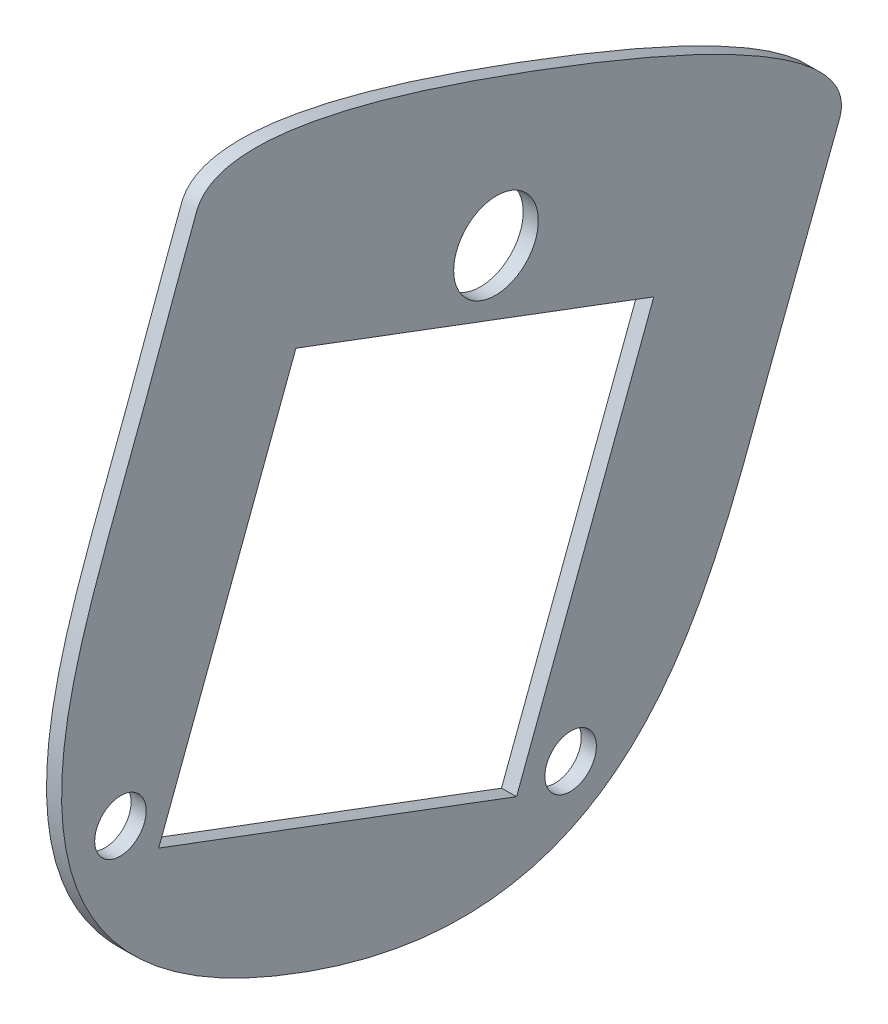
SolidWorks part; units mm, degrees
ref_plane "Front Plane" through (0, 0, 0) normal (0, 0, 1) x (1, 0, 0)
ref_plane "Top Plane" through (0, 0, 0) normal (0, 1, 0) x (1, 0, 0)
ref_plane "Right Plane" through (0, 0, 0) normal (1, 0, 0) x (0, 0, -1)
sketch "Sketch2" plane through (-865.3739, -0.0001, 10.9842) normal (-0.9999, 0, 0.0127) x (0.0127, 0, 0.9999)
  circle A0 centre (-17.1866, -9.2159) radius 6 construction
  circle A1 centre (105.1276, 37.6907) radius 6 construction
  circle A2 centre (-17.1866, -9.2159) radius 6
  circle A3 centre (105.1276, 37.6907) radius 6
  circle A4 centre (2.5155, 122.3361) radius 11.5 construction
  circle A5 centre (2.5155, 122.3361) radius 11.5
  point P0 (86.5551, 152.6282)
  point P1 (81.9504, 150.6796)
  dimension "D4" = 23
  dimension "D1" = 5
ref_plane "Plane1" through (-1179.5486, -0.0001, 14.972) normal (-0.9999, 0, 0.0127) x (0.0127, 0, 0.9999)
sketch "Sketch3" plane through (-1179.5486, -0.0001, 14.972) normal (-0.9999, 0, 0.0127) x (0.0127, 0, 0.9999)
  line L2 (-2.4987, -10.0092) -> (94.7364, 27.2797)
  line L6 (94.7364, 27.2797) -> (57.4475, 124.5149)
  line L7 (57.4475, 124.5149) -> (-39.7876, 87.2259)
  line L8 (-39.7876, 87.2259) -> (-2.4987, -10.0092)
  circle A3 centre (105.1276, 37.6907) radius 7
  circle A8 centre (3.0884, 120.8422) radius 11.5
  circle A9 centre (-17.1866, -9.2159) radius 7
  spline S0 degree 3 poles (84.5877, 169.5548) (84.1591, 170.6141) (83.6114, 171.6458) (82.4825, 172.9682) (81.1275, 174.0328) (79.6255, 174.8519) (78.0481, 175.4677) (75.8837, 176.0674) (73.1375, 176.4938) (69.8483, 176.6685) (66.5932, 176.6095) (63.379, 176.3823) (60.2073, 176.0282) (57.0754, 175.5759) (53.9806, 175.0444) (50.9193, 174.4483) (47.8886, 173.7975) (44.8855, 173.1008) (40.9147, 172.1178) (36.0066, 170.8019) (30.1862, 169.1128) (24.4167, 167.3312) (18.6809, 165.471) (12.9629, 163.5374) (7.2468, 161.5366) (-0.3928, 158.7797) (-6.166, 156.6131) (-13.9483, 153.6286) (-19.6897, 151.3795) (-27.2134, 148.3214) (-32.8014, 145.9872) (-38.3459, 143.6017) (-43.8547, 141.1498) (-49.3359, 138.6168) (-54.7932, 135.9811) (-59.3225, 133.6777) (-62.9324, 131.7536) (-65.6313, 130.2638) (-68.3201, 128.7213) (-70.995, 127.1176) (-73.6517, 125.4434) (-76.283, 123.6856) (-78.8782, 121.8282) (-81.4203, 119.8479) (-83.8804, 117.7153) (-86.2094, 115.386) (-87.9665, 113.2326) (-89.1751, 111.3395) (-89.9363, 109.8267) (-90.5056, 108.2133) (-90.8014, 106.5155) (-90.7567, 104.7772) (-90.474, 103.6437) (-90.0844, 102.5695) (-89.841, 101.912) (-89.5415, 101.1241) (-89.3902, 100.7305) (-89.238, 100.337) (-89.086, 99.9434) (-88.9335, 99.5497) (-88.7301, 99.0246) (-88.3735, 98.1053) (-87.8622, 96.7909) (-87.2459, 95.2119) (-86.6271, 93.6311) (-86.006, 92.0484) (-85.3828, 90.4637) (-84.7576, 88.8772) (-84.1306, 87.2885) (-83.5021, 85.6979) (-82.662, 83.5742) (-81.6087, 80.9142) (-80.341, 77.7134) (-79.0707, 74.5033) (-77.7994, 71.2836) (-76.5287, 68.0539) (-75.2594, 64.814) (-73.9927, 61.5637) (-72.7309, 58.3024) (-71.4763, 55.0294) (-69.81, 50.6514) (-67.733, 45.1559) (-65.1929, 38.5485) (-63.0021, 33.047) (-61.1797, 28.6615) (-60.0063, 25.9297) (-59.0438, 23.7513) (-58.3093, 22.1218) (-57.5611, 20.497) (-56.7986, 18.8776) (-56.0207, 17.2642) (-55.227, 15.6574) (-54.4159, 14.0579) (-52.7551, 10.8759) (-50.1136, 6.1705) (-46.2141, 0.1062) (-41.8798, -5.6826) (-37.071, -11.0955) (-31.7493, -16.031) (-26.8927, -19.6435) (-22.7717, -22.1827) (-18.509, -24.4734) (-12.9357, -26.8488) (-5.9687, -28.8976) (1.1735, -30.1678) (8.3946, -30.7243) (15.6292, -30.6392) (22.8222, -29.9927) (29.9449, -28.8562) (36.9714, -27.3105) (46.201, -24.7823) (52.9582, -22.4509) (61.8197, -19.0525) (68.4041, -16.2675) (76.9584, -11.9755) (83.2171, -8.426) (89.2737, -4.508) (95.0546, -0.1787) (100.4909, 4.596) (105.488, 9.8386) (109.9491, 15.5591) (113.7592, 21.7413) (116.3146, 27.2342) (117.9522, 31.7877) (119.3182, 36.4313) (120.5136, 42.3647) (121.1702, 49.5927) (121.1263, 56.8326) (120.4783, 64.0347) (119.3229, 71.151) (118.1408, 76.4157) (117.2481, 79.8921) (116.7817, 81.6236) (116.2975, 83.349) (115.7971, 85.0687) (115.2813, 86.7826) (114.7512, 88.4909) (114.2078, 90.1937) (113.467, 92.4568) (112.5129, 95.2725) (110.9356, 99.7518) (108.8862, 105.3072) (106.3571, 111.9184) (104.227, 117.3933) (102.5388, 121.7627) (101.2832, 125.0351) (100.0408, 128.3038) (98.8095, 131.5676) (97.5869, 134.8253) (96.3723, 138.0765) (95.1647, 141.3206) (93.9629, 144.5568) (92.7653, 147.7846) (91.7699, 150.4668) (90.9746, 152.6077) (90.3784, 154.2108) (89.7824, 155.8113) (89.1863, 157.4091) (88.5902, 159.0041) (87.9938, 160.5963) (87.3968, 162.1856) (86.7993, 163.7719) (86.3006, 165.0911) (85.9511, 166.0132) (85.7512, 166.5397) (85.6013, 166.9344) (85.4511, 167.3288) (85.3012, 167.7231) (85.1505, 168.117) (84.8464, 168.9032) (84.5877, 169.5548) (84.1591, 170.6141) (83.6114, 171.6458) knots -0.00321 -0.002568 0 0 0.002678 0.005356 0.008033 0.010711 0.013389 0.016067 0.021422 0.026778 0.032133 0.037489 0.042844 0.0482 0.053555 0.058911 0.064266 0.069622 0.074977 0.085688 0.096399 0.10711 0.117821 0.128532 0.139243 0.149955 0.171377 0.171377 0.192798 0.203509 0.21422 0.224931 0.235641 0.246352 0.257063 0.267774 0.273129 0.278485 0.28384 0.289196 0.294551 0.299906 0.305262 0.310617 0.315973 0.321328 0.326683 0.329361 0.332039 0.334717 0.337394 0.340072 0.34275 0.34275 0.345317 0.345958 0.3466 0.347242 0.347884 0.348525 0.349167 0.350451 0.353018 0.355585 0.358152 0.360719 0.363286 0.365853 0.36842 0.370987 0.373554 0.378688 0.383822 0.388956 0.39409 0.399224 0.404358 0.409492 0.414626 0.419761 0.424895 0.435163 0.445431 0.455699 0.460833 0.465967 0.468534 0.471101 0.473668 0.476235 0.478802 0.481369 0.483936 0.486503 0.496771 0.507039 0.517308 0.527576 0.537844 0.548112 0.553246 0.55838 0.568648 0.578916 0.589184 0.599453 0.609721 0.619989 0.630257 0.640525 0.650793 0.671329 0.671329 0.691871 0.702142 0.712413 0.722684 0.732955 0.743226 0.753497 0.763768 0.774039 0.78431 0.789445 0.794581 0.804852 0.815123 0.825394 0.835665 0.845936 0.856207 0.858774 0.861342 0.86391 0.866478 0.869045 0.871613 0.874181 0.876748 0.881884 0.887019 0.89729 0.907561 0.917832 0.922968 0.928103 0.933239 0.938374 0.94351 0.948645 0.953781 0.958916 0.964052 0.969187 0.971755 0.974323 0.97689 0.979458 0.982026 0.984594 0.987161 0.989729 0.992297 0.993581 0.994223 0.994865 0.995506 0.996148 0.99679 0.997432 1 1 1.002678 1.005356 1.008033 only from (84.3779, 170.0733) to (84.3779, 170.0733)
  spline S1 degree 3 poles (84.5877, 169.5548) (84.1591, 170.6141) (83.6114, 171.6458) (82.4825, 172.9682) (81.1275, 174.0328) (79.6255, 174.8519) (78.0481, 175.4677) (75.8837, 176.0674) (73.1375, 176.4938) (69.8483, 176.6685) (66.5932, 176.6095) (63.379, 176.3823) (60.2073, 176.0282) (57.0754, 175.5759) (53.9806, 175.0444) (50.9193, 174.4483) (47.8886, 173.7975) (44.8855, 173.1008) (40.9147, 172.1178) (36.0066, 170.8019) (30.1862, 169.1128) (24.4167, 167.3312) (18.6809, 165.471) (12.9629, 163.5374) (7.2468, 161.5366) (-0.3928, 158.7797) (-6.166, 156.6131) (-13.9483, 153.6286) (-19.6897, 151.3795) (-27.2134, 148.3214) (-32.8014, 145.9872) (-38.3459, 143.6017) (-43.8547, 141.1498) (-49.3359, 138.6168) (-54.7932, 135.9811) (-59.3225, 133.6777) (-62.9324, 131.7536) (-65.6313, 130.2638) (-68.3201, 128.7213) (-70.995, 127.1176) (-73.6517, 125.4434) (-76.283, 123.6856) (-78.8782, 121.8282) (-81.4203, 119.8479) (-83.8804, 117.7153) (-86.2094, 115.386) (-87.9665, 113.2326) (-89.1751, 111.3395) (-89.9363, 109.8267) (-90.5056, 108.2133) (-90.8014, 106.5155) (-90.7567, 104.7772) (-90.474, 103.6437) (-90.0844, 102.5695) (-89.841, 101.912) (-89.5415, 101.1241) (-89.3902, 100.7305) (-89.238, 100.337) (-89.086, 99.9434) (-88.9335, 99.5497) (-88.7301, 99.0246) (-88.3735, 98.1053) (-87.8622, 96.7909) (-87.2459, 95.2119) (-86.6271, 93.6311) (-86.006, 92.0484) (-85.3828, 90.4637) (-84.7576, 88.8772) (-84.1306, 87.2885) (-83.5021, 85.6979) (-82.662, 83.5742) (-81.6087, 80.9142) (-80.341, 77.7134) (-79.0707, 74.5033) (-77.7994, 71.2836) (-76.5287, 68.0539) (-75.2594, 64.814) (-73.9927, 61.5637) (-72.7309, 58.3024) (-71.4763, 55.0294) (-69.81, 50.6514) (-67.733, 45.1559) (-65.1929, 38.5485) (-63.0021, 33.047) (-61.1797, 28.6615) (-60.0063, 25.9297) (-59.0438, 23.7513) (-58.3093, 22.1218) (-57.5611, 20.497) (-56.7986, 18.8776) (-56.0207, 17.2642) (-55.227, 15.6574) (-54.4159, 14.0579) (-52.7551, 10.8759) (-50.1136, 6.1705) (-46.2141, 0.1062) (-41.8798, -5.6826) (-37.071, -11.0955) (-31.7493, -16.031) (-26.8927, -19.6435) (-22.7717, -22.1827) (-18.509, -24.4734) (-12.9357, -26.8488) (-5.9687, -28.8976) (1.1735, -30.1678) (8.3946, -30.7243) (15.6292, -30.6392) (22.8222, -29.9927) (29.9449, -28.8562) (36.9714, -27.3105) (46.201, -24.7823) (52.9582, -22.4509) (61.8197, -19.0525) (68.4041, -16.2675) (76.9584, -11.9755) (83.2171, -8.426) (89.2737, -4.508) (95.0546, -0.1787) (100.4909, 4.596) (105.488, 9.8386) (109.9491, 15.5591) (113.7592, 21.7413) (116.3146, 27.2342) (117.9522, 31.7877) (119.3182, 36.4313) (120.5136, 42.3647) (121.1702, 49.5927) (121.1263, 56.8326) (120.4783, 64.0347) (119.3229, 71.151) (118.1408, 76.4157) (117.2481, 79.8921) (116.7817, 81.6236) (116.2975, 83.349) (115.7971, 85.0687) (115.2813, 86.7826) (114.7512, 88.4909) (114.2078, 90.1937) (113.467, 92.4568) (112.5129, 95.2725) (110.9356, 99.7518) (108.8862, 105.3072) (106.3571, 111.9184) (104.227, 117.3933) (102.5388, 121.7627) (101.2832, 125.0351) (100.0408, 128.3038) (98.8095, 131.5676) (97.5869, 134.8253) (96.3723, 138.0765) (95.1647, 141.3206) (93.9629, 144.5568) (92.7653, 147.7846) (91.7699, 150.4668) (90.9746, 152.6077) (90.3784, 154.2108) (89.7824, 155.8113) (89.1863, 157.4091) (88.5902, 159.0041) (87.9938, 160.5963) (87.3968, 162.1856) (86.7993, 163.7719) (86.3006, 165.0911) (85.9511, 166.0132) (85.7512, 166.5397) (85.6013, 166.9344) (85.4511, 167.3288) (85.3012, 167.7231) (85.1505, 168.117) (84.8464, 168.9032) (84.5877, 169.5548) (84.1591, 170.6141) (83.6114, 171.6458) knots -0.00321 -0.002568 0 0 0.002678 0.005356 0.008033 0.010711 0.013389 0.016067 0.021422 0.026778 0.032133 0.037489 0.042844 0.0482 0.053555 0.058911 0.064266 0.069622 0.074977 0.085688 0.096399 0.10711 0.117821 0.128532 0.139243 0.149955 0.171377 0.171377 0.192798 0.203509 0.21422 0.224931 0.235641 0.246352 0.257063 0.267774 0.273129 0.278485 0.28384 0.289196 0.294551 0.299906 0.305262 0.310617 0.315973 0.321328 0.326683 0.329361 0.332039 0.334717 0.337394 0.340072 0.34275 0.34275 0.345317 0.345958 0.3466 0.347242 0.347884 0.348525 0.349167 0.350451 0.353018 0.355585 0.358152 0.360719 0.363286 0.365853 0.36842 0.370987 0.373554 0.378688 0.383822 0.388956 0.39409 0.399224 0.404358 0.409492 0.414626 0.419761 0.424895 0.435163 0.445431 0.455699 0.460833 0.465967 0.468534 0.471101 0.473668 0.476235 0.478802 0.481369 0.483936 0.486503 0.496771 0.507039 0.517308 0.527576 0.537844 0.548112 0.553246 0.55838 0.568648 0.578916 0.589184 0.599453 0.609721 0.619989 0.630257 0.640525 0.650793 0.671329 0.671329 0.691871 0.702142 0.712413 0.722684 0.732955 0.743226 0.753497 0.763768 0.774039 0.78431 0.789445 0.794581 0.804852 0.815123 0.825394 0.835665 0.845936 0.856207 0.858774 0.861342 0.86391 0.866478 0.869045 0.871613 0.874181 0.876748 0.881884 0.887019 0.89729 0.907561 0.917832 0.922968 0.928103 0.933239 0.938374 0.94351 0.948645 0.953781 0.958916 0.964052 0.969187 0.971755 0.974323 0.97689 0.979458 0.982026 0.984594 0.987161 0.989729 0.992297 0.993581 0.994223 0.994865 0.995506 0.996148 0.99679 0.997432 1 1 1.002678 1.005356 1.008033 only from (84.3779, 170.0733) to (84.3779, 170.0733)
  spline S2 degree 3 poles (79.7703, 168.0973) (79.654, 168.385) (79.5608, 168.567) (79.34, 168.909) (79.2107, 169.0695) (78.782, 169.5156) (78.4531, 169.7564) (77.7463, 170.1738) (77.3742, 170.347) (76.6181, 170.646) (76.2313, 170.7718) (75.4457, 170.9901) (75.0459, 171.0829) (74.2475, 171.2414) (73.8476, 171.3072) (72.6462, 171.473) (71.8432, 171.5429) (69.4298, 171.6691) (67.8151, 171.6433) (64.5792, 171.4656) (62.9671, 171.312) (59.7615, 170.9206) (58.1658, 170.6823) (54.9849, 170.1436) (53.3996, 169.8431) (48.656, 168.8688) (45.5068, 168.1227) (39.2498, 166.5091) (36.1403, 165.6406) (29.9484, 163.8155) (26.8662, 162.8586) (17.65, 159.8886) (11.5458, 157.7754) (-0.6049, 153.3792) (-6.6499, 151.0973) (-18.6886, 146.4029) (-24.6805, 143.9847) (-36.5791, 138.946) (-42.4872, 136.3273) (-51.2341, 132.1553) (-54.1301, 130.7232) (-59.8634, 127.7454) (-62.7011, 126.2002) (-66.8856, 123.7579) (-68.2675, 122.9231) (-70.9987, 121.2004) (-72.3487, 120.3119) (-74.9994, 118.4656) (-76.2997, 117.5087) (-78.8252, 115.4929) (-80.0492, 114.4377) (-81.7749, 112.7382) (-82.3328, 112.1498) (-83.3836, 110.9299) (-83.8771, 110.2969) (-84.5427, 109.2937) (-84.7517, 108.95) (-85.1321, 108.2356) (-85.3048, 107.8624) (-85.5131, 107.2891) (-85.5741, 107.0954) (-85.6734, 106.7005) (-85.7118, 106.4978) (-85.7567, 106.0923) (-85.7631, 105.8894) (-85.7375, 105.4833) (-85.7033, 105.2783) (-85.5978, 104.885) (-85.5239, 104.6959) (-85.3844, 104.3148) (-85.3142, 104.1244) (-85.1021, 103.5537) (-84.9587, 103.174) (-84.5227, 102.0368) (-84.2284, 101.28) (-83.3473, 99.0091) (-82.7572, 97.4963) (-77.4279, 83.8874) (-72.5683, 71.8388) (-66.7371, 56.6822) (-65.5847, 53.6454) (-63.2813, 47.5713) (-62.1268, 44.5353) (-59.771, 38.4819) (-58.5707, 35.464) (-56.7026, 30.9639) (-56.0686, 29.4684) (-54.7723, 26.4884) (-54.1097, 25.0035) (-50.7192, 17.6341) (-47.7589, 11.8968) (-42.5832, 3.7604) (-40.7366, 1.1258) (-37.7313, -2.6759) (-36.6901, -3.9179) (-35.0604, -5.7377) (-34.5059, -6.337) (-33.3724, -7.5201) (-32.7922, -8.1052) (-29.8441, -10.9713) (-27.345, -13.0666) (-23.3611, -15.8788) (-21.9939, -16.761) (-19.1769, -18.4096) (-17.7261, -19.1766) (-10.2663, -22.7) (-3.9825, -24.3776) (3.3729, -25.2321) (4.1924, -25.3124) (5.8269, -25.4445) (6.6433, -25.4963) (9.09, -25.6118) (10.7178, -25.6352) (15.5924, -25.5618) (18.8302, -25.3221) (23.6723, -24.7256) (25.2838, -24.487) (28.5025, -23.9384) (30.1115, -23.628) (34.9193, -22.6026) (38.0868, -21.7953) (44.3622, -19.9846) (47.4703, -18.982) (52.0947, -17.3537) (53.6299, -16.7903) (56.6886, -15.6251) (58.2124, -15.0236) (62.7493, -13.1641) (65.733, -11.8489) (71.6057, -9.0437) (74.4945, -7.5535) (80.1538, -4.3544) (82.9251, -2.6472) (86.9704, 0.1194) (88.3001, 1.0763) (90.263, 2.5701) (90.9119, 3.0777) (92.1913, 4.1078) (92.8227, 4.6309) (95.9368, 7.2882) (98.2906, 9.5479) (101.5765, 13.1758) (102.631, 14.4249) (104.1451, 16.3643) (104.6385, 17.0217) (105.6014, 18.3598) (106.0705, 19.0401) (108.3321, 22.4686) (109.8916, 25.3227) (112.4961, 31.2603) (113.5391, 34.3445) (114.5167, 38.3452) (114.696, 39.1533) (115.0193, 40.7681) (115.1639, 41.5767) (115.5483, 44.0063) (115.7388, 45.6309) (116.1311, 50.5177) (116.1533, 53.7931) (115.9328, 57.9055) (115.8763, 58.7278) (115.7406, 60.3643) (115.6615, 61.1797) (115.3922, 63.6178) (115.1705, 65.2327) (114.3953, 70.0494) (113.7318, 73.2236) (112.1864, 79.5171) (111.3038, 82.6361) (109.3954, 88.8382) (108.3675, 91.9207) (106.215, 98.0612) (105.0894, 101.1202) (102.7905, 107.2203) (101.6164, 110.261) (99.26, 116.3391) (98.0812, 119.3779) (95.7512, 125.4661) (94.5998, 128.5155) (91.1648, 137.6705) (88.9043, 143.7849) (85.4993, 152.9511) (84.362, 156.0057) (82.6444, 160.5831) (82.0699, 162.1082) (81.2041, 164.3942) (80.9151, 165.1561) (80.4796, 166.2982) (80.3329, 166.6783) (80.1095, 167.2472) (79.9971, 167.5314) (79.8836, 167.8152) (79.8078, 168.0043) (79.7703, 168.0973) (79.654, 168.385) (79.5608, 168.567) knots -0.000488 -0.000488 0 0 0.000977 0.000977 0.001953 0.001953 0.003906 0.003906 0.005859 0.005859 0.007812 0.007812 0.009766 0.009766 0.011719 0.011719 0.015625 0.015625 0.023437 0.023437 0.03125 0.03125 0.039062 0.039062 0.046875 0.046875 0.0625 0.0625 0.078125 0.078125 0.09375 0.09375 0.125 0.125 0.15625 0.15625 0.1875 0.1875 0.21875 0.21875 0.234375 0.234375 0.25 0.25 0.257812 0.257812 0.265625 0.265625 0.273437 0.273437 0.28125 0.28125 0.285156 0.285156 0.289062 0.289062 0.291016 0.291016 0.292969 0.292969 0.293945 0.293945 0.294922 0.294922 0.295898 0.295898 0.296875 0.296875 0.297852 0.297852 0.298828 0.298828 0.300781 0.300781 0.304687 0.304687 0.3125 0.3125 0.375 0.375 0.390625 0.390625 0.40625 0.40625 0.421875 0.421875 0.429687 0.429687 0.4375 0.4375 0.46875 0.46875 0.484375 0.484375 0.492187 0.492187 0.496094 0.496094 0.5 0.5 0.515625 0.515625 0.523437 0.523437 0.53125 0.53125 0.5625 0.5625 0.566406 0.566406 0.570312 0.570312 0.578125 0.578125 0.59375 0.59375 0.601562 0.601562 0.609375 0.609375 0.625 0.625 0.640625 0.640625 0.648437 0.648437 0.65625 0.65625 0.671875 0.671875 0.6875 0.6875 0.703125 0.703125 0.710937 0.710937 0.714844 0.714844 0.71875 0.71875 0.734375 0.734375 0.742187 0.742187 0.746094 0.746094 0.75 0.75 0.765625 0.765625 0.78125 0.78125 0.785156 0.785156 0.789062 0.789062 0.796875 0.796875 0.8125 0.8125 0.816406 0.816406 0.820312 0.820312 0.828125 0.828125 0.84375 0.84375 0.859375 0.859375 0.875 0.875 0.890625 0.890625 0.90625 0.90625 0.921875 0.921875 0.9375 0.9375 0.96875 0.96875 0.984375 0.984375 0.992187 0.992187 0.996094 0.996094 0.998047 0.998047 0.999023 0.999512 0.999512 1 1 1.000977 1.000977 1.001953 only from (79.7315, 168.1932) to (79.7315, 168.1932)
  spline S3 degree 3 poles (79.7703, 168.0973) (79.654, 168.385) (79.5608, 168.567) (79.34, 168.909) (79.2107, 169.0695) (78.782, 169.5156) (78.4531, 169.7564) (77.7463, 170.1738) (77.3742, 170.347) (76.6181, 170.646) (76.2313, 170.7718) (75.4457, 170.9901) (75.0459, 171.0829) (74.2475, 171.2414) (73.8476, 171.3072) (72.6462, 171.473) (71.8432, 171.5429) (69.4298, 171.6691) (67.8151, 171.6433) (64.5792, 171.4656) (62.9671, 171.312) (59.7615, 170.9206) (58.1658, 170.6823) (54.9849, 170.1436) (53.3996, 169.8431) (48.656, 168.8688) (45.5068, 168.1227) (39.2498, 166.5091) (36.1403, 165.6406) (29.9484, 163.8155) (26.8662, 162.8586) (17.65, 159.8886) (11.5458, 157.7754) (-0.6049, 153.3792) (-6.6499, 151.0973) (-18.6886, 146.4029) (-24.6805, 143.9847) (-36.5791, 138.946) (-42.4872, 136.3273) (-51.2341, 132.1553) (-54.1301, 130.7232) (-59.8634, 127.7454) (-62.7011, 126.2002) (-66.8856, 123.7579) (-68.2675, 122.9231) (-70.9987, 121.2004) (-72.3487, 120.3119) (-74.9994, 118.4656) (-76.2997, 117.5087) (-78.8252, 115.4929) (-80.0492, 114.4377) (-81.7749, 112.7382) (-82.3328, 112.1498) (-83.3836, 110.9299) (-83.8771, 110.2969) (-84.5427, 109.2937) (-84.7517, 108.95) (-85.1321, 108.2356) (-85.3048, 107.8624) (-85.5131, 107.2891) (-85.5741, 107.0954) (-85.6734, 106.7005) (-85.7118, 106.4978) (-85.7567, 106.0923) (-85.7631, 105.8894) (-85.7375, 105.4833) (-85.7033, 105.2783) (-85.5978, 104.885) (-85.5239, 104.6959) (-85.3844, 104.3148) (-85.3142, 104.1244) (-85.1021, 103.5537) (-84.9587, 103.174) (-84.5227, 102.0368) (-84.2284, 101.28) (-83.3473, 99.0091) (-82.7572, 97.4963) (-77.4279, 83.8874) (-72.5683, 71.8388) (-66.7371, 56.6822) (-65.5847, 53.6454) (-63.2813, 47.5713) (-62.1268, 44.5353) (-59.771, 38.4819) (-58.5707, 35.464) (-56.7026, 30.9639) (-56.0686, 29.4684) (-54.7723, 26.4884) (-54.1097, 25.0035) (-50.7192, 17.6341) (-47.7589, 11.8968) (-42.5832, 3.7604) (-40.7366, 1.1258) (-37.7313, -2.6759) (-36.6901, -3.9179) (-35.0604, -5.7377) (-34.5059, -6.337) (-33.3724, -7.5201) (-32.7922, -8.1052) (-29.8441, -10.9713) (-27.345, -13.0666) (-23.3611, -15.8788) (-21.9939, -16.761) (-19.1769, -18.4096) (-17.7261, -19.1766) (-10.2663, -22.7) (-3.9825, -24.3776) (3.3729, -25.2321) (4.1924, -25.3124) (5.8269, -25.4445) (6.6433, -25.4963) (9.09, -25.6118) (10.7178, -25.6352) (15.5924, -25.5618) (18.8302, -25.3221) (23.6723, -24.7256) (25.2838, -24.487) (28.5025, -23.9384) (30.1115, -23.628) (34.9193, -22.6026) (38.0868, -21.7953) (44.3622, -19.9846) (47.4703, -18.982) (52.0947, -17.3537) (53.6299, -16.7903) (56.6886, -15.6251) (58.2124, -15.0236) (62.7493, -13.1641) (65.733, -11.8489) (71.6057, -9.0437) (74.4945, -7.5535) (80.1538, -4.3544) (82.9251, -2.6472) (86.9704, 0.1194) (88.3001, 1.0763) (90.263, 2.5701) (90.9119, 3.0777) (92.1913, 4.1078) (92.8227, 4.6309) (95.9368, 7.2882) (98.2906, 9.5479) (101.5765, 13.1758) (102.631, 14.4249) (104.1451, 16.3643) (104.6385, 17.0217) (105.6014, 18.3598) (106.0705, 19.0401) (108.3321, 22.4686) (109.8916, 25.3227) (112.4961, 31.2603) (113.5391, 34.3445) (114.5167, 38.3452) (114.696, 39.1533) (115.0193, 40.7681) (115.1639, 41.5767) (115.5483, 44.0063) (115.7388, 45.6309) (116.1311, 50.5177) (116.1533, 53.7931) (115.9328, 57.9055) (115.8763, 58.7278) (115.7406, 60.3643) (115.6615, 61.1797) (115.3922, 63.6178) (115.1705, 65.2327) (114.3953, 70.0494) (113.7318, 73.2236) (112.1864, 79.5171) (111.3038, 82.6361) (109.3954, 88.8382) (108.3675, 91.9207) (106.215, 98.0612) (105.0894, 101.1202) (102.7905, 107.2203) (101.6164, 110.261) (99.26, 116.3391) (98.0812, 119.3779) (95.7512, 125.4661) (94.5998, 128.5155) (91.1648, 137.6705) (88.9043, 143.7849) (85.4993, 152.9511) (84.362, 156.0057) (82.6444, 160.5831) (82.0699, 162.1082) (81.2041, 164.3942) (80.9151, 165.1561) (80.4796, 166.2982) (80.3329, 166.6783) (80.1095, 167.2472) (79.9971, 167.5314) (79.8836, 167.8152) (79.8078, 168.0043) (79.7703, 168.0973) (79.654, 168.385) (79.5608, 168.567) knots -0.000488 -0.000488 0 0 0.000977 0.000977 0.001953 0.001953 0.003906 0.003906 0.005859 0.005859 0.007812 0.007812 0.009766 0.009766 0.011719 0.011719 0.015625 0.015625 0.023437 0.023437 0.03125 0.03125 0.039062 0.039062 0.046875 0.046875 0.0625 0.0625 0.078125 0.078125 0.09375 0.09375 0.125 0.125 0.15625 0.15625 0.1875 0.1875 0.21875 0.21875 0.234375 0.234375 0.25 0.25 0.257812 0.257812 0.265625 0.265625 0.273437 0.273437 0.28125 0.28125 0.285156 0.285156 0.289062 0.289062 0.291016 0.291016 0.292969 0.292969 0.293945 0.293945 0.294922 0.294922 0.295898 0.295898 0.296875 0.296875 0.297852 0.297852 0.298828 0.298828 0.300781 0.300781 0.304687 0.304687 0.3125 0.3125 0.375 0.375 0.390625 0.390625 0.40625 0.40625 0.421875 0.421875 0.429687 0.429687 0.4375 0.4375 0.46875 0.46875 0.484375 0.484375 0.492187 0.492187 0.496094 0.496094 0.5 0.5 0.515625 0.515625 0.523437 0.523437 0.53125 0.53125 0.5625 0.5625 0.566406 0.566406 0.570312 0.570312 0.578125 0.578125 0.59375 0.59375 0.601562 0.601562 0.609375 0.609375 0.625 0.625 0.640625 0.640625 0.648437 0.648437 0.65625 0.65625 0.671875 0.671875 0.6875 0.6875 0.703125 0.703125 0.710937 0.710937 0.714844 0.714844 0.71875 0.71875 0.734375 0.734375 0.742187 0.742187 0.746094 0.746094 0.75 0.75 0.765625 0.765625 0.78125 0.78125 0.785156 0.785156 0.789062 0.789062 0.796875 0.796875 0.8125 0.8125 0.816406 0.816406 0.820312 0.820312 0.828125 0.828125 0.84375 0.84375 0.859375 0.859375 0.875 0.875 0.890625 0.890625 0.90625 0.90625 0.921875 0.921875 0.9375 0.9375 0.96875 0.96875 0.984375 0.984375 0.992187 0.992187 0.996094 0.996094 0.998047 0.998047 0.999023 0.999512 0.999512 1 1 1.000977 1.000977 1.001953 only from (79.7315, 168.1932) to (79.7315, 168.1932)
extrude "Boss-Extrude1" add sketch "Sketch3" against normal blind 4 contours S1 S3 | S3 A8 A9 A3 region at (-1179.9823, -9.6438, -19.1964) region at (-1179.9212, -7.4934, -14.382)
